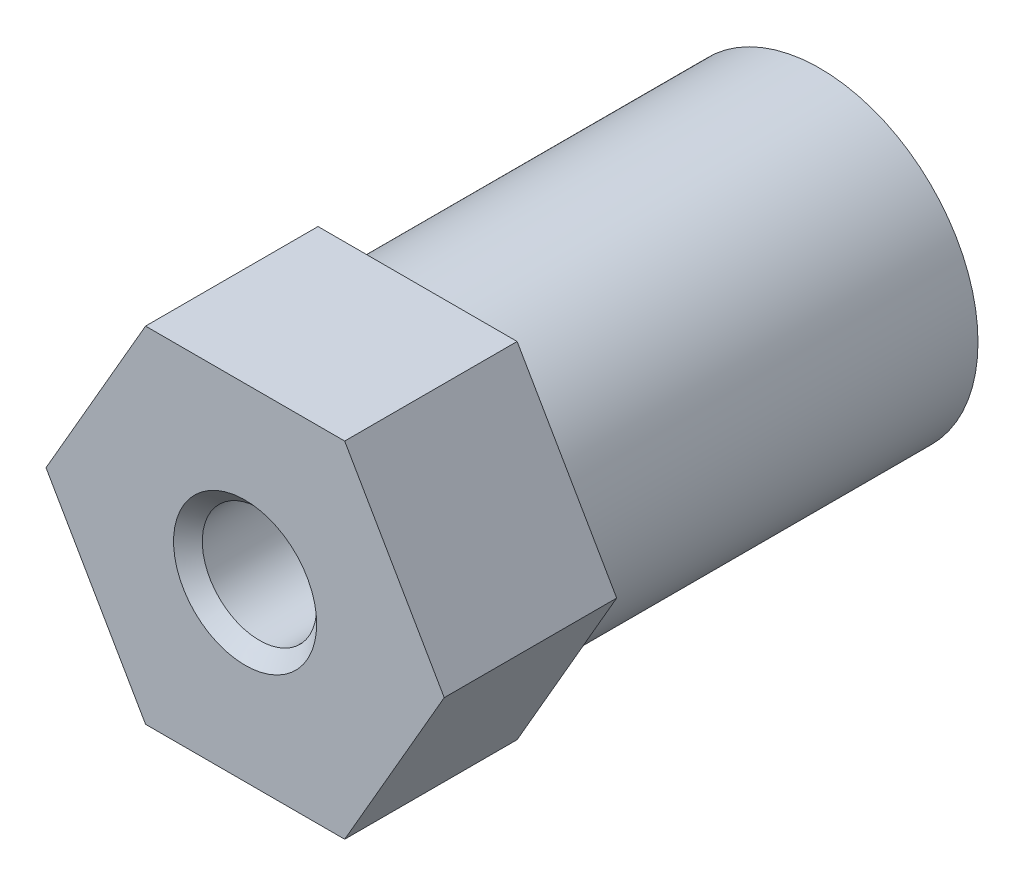
SolidWorks part; units mm, degrees
material "Brass"
ref_plane "Front Plane" through (0, 0, 0) normal (0, 0, 1) x (1, 0, 0)
ref_plane "Top Plane" through (0, 0, 0) normal (0, 1, 0) x (1, 0, 0)
ref_plane "Right Plane" through (0, 0, 0) normal (1, 0, 0) x (0, 0, -1)
sketch "Sketch1" plane through (0, 0, 0) normal (0, 0, 1) x (1, 0, 0)
  circle A0 centre (0, 0) radius 5.5
  dimension "D1" = 11
extrude "Boss-Extrude1" add sketch "Sketch1" along normal blind 14
sketch "Sketch2" plane through (0, 0, 14) normal (0, 0, 1) x (1, 0, 0)
  line L1 (-6.9282, 0) -> (-3.4641, -6)
  line L2 (-3.4641, -6) -> (3.4641, -6)
  line L3 (3.4641, -6) -> (6.9282, 0)
  line L4 (6.9282, 0) -> (3.4641, 6)
  line L5 (3.4641, 6) -> (-3.4641, 6)
  line L6 (-3.4641, 6) -> (-6.9282, 0)
  circle A0 centre (0, 0) radius 6 construction
  dimension "D1" = 12
  dimension "D2" = 3.4641
extrude "Boss-Extrude2" add sketch "Sketch2" along normal blind 6
sketch "Sketch3" plane through (0, 0, 20) normal (0, 0, 1) x (1, 0, 0)
  circle A0 centre (0, 0) radius 1.99
  dimension "D1" = 3.98
extrude "Cut-Extrude1" cut sketch "Sketch3" against normal blind 8
sketch "Sketch4" plane through (0, 0, 0) normal (0, 0, -1) x (-1, 0, 0)
  line L1 (-2.2361, 2) -> (2.2361, 2)
  line L3 (-2.2361, -2) -> (2.2361, -2)
  arc A0 (-2.2361, 2) -> (-2.2361, -2) centre (0, 0) ccw
  arc A1 (2.2361, -2) -> (2.2361, 2) centre (0, 0) ccw
  point P7 (-3.7509, 1.5403)
  point P8 (3.7033, -1.5018)
  dimension "D1" = 6
  dimension "D2" = 2
  dimension "D3" = 2
extrude "Cut-Extrude2" cut sketch "Sketch4" against normal blind 12
sketch "Sketch5" plane through (0, 0, 0) normal (0, 0, -1) x (-1, 0, 0)
  arc A0 (-2.2361, 2) -> (-2.2361, -2) centre (0, 0) ccw construction
  circle A3 centre (0, 0) radius 3
  point P6 (-2.2361, -2.144)
extrude "Cut-Extrude3" cut sketch "Sketch5" against normal blind 1.5
fillet "Fillet2" radius 0.5 2 edges at (0, 2, 1.5) (0, -2, 1.5)
chamfer "Chamfer1" distance 0.5 angle 45 1 edges at (1.99, 0, 20)
